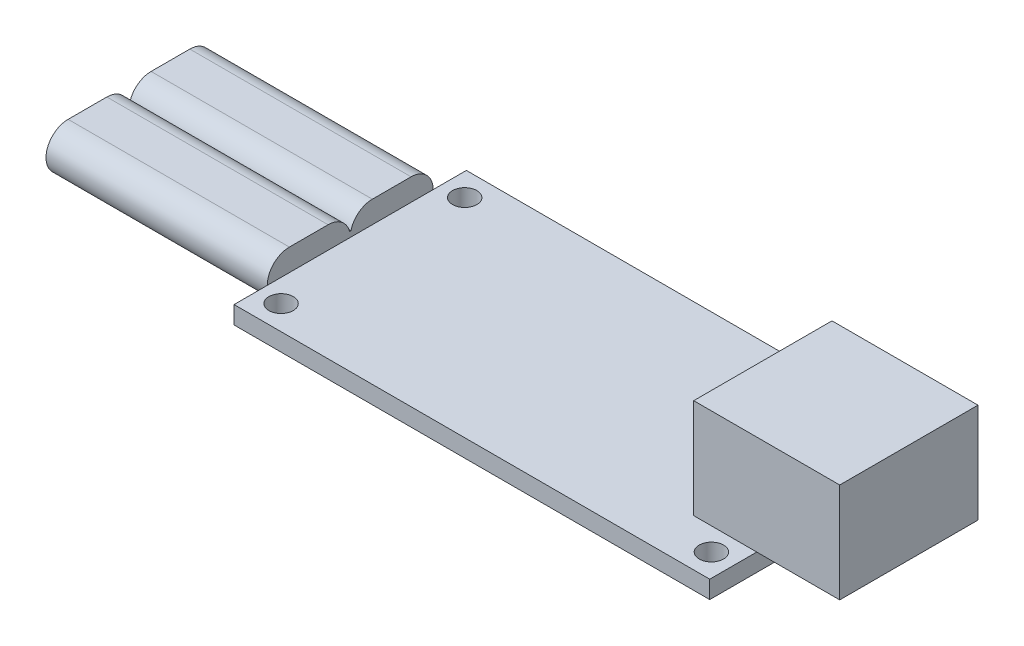
SolidWorks part; units mm, degrees
ref_plane "Płaszczyzna przednia" through (0, 0, 0) normal (0, 0, 1) x (1, 0, 0)
ref_plane "Płaszczyzna górna" through (0, 0, 0) normal (0, 1, 0) x (1, 0, 0)
ref_plane "Płaszczyzna prawa" through (0, 0, 0) normal (1, 0, 0) x (0, 0, -1)
sketch "Sketch1" plane through (0, 0, 0) normal (0, 1, 0) x (1, 0, 0)
  line L0 (21.5, 21) -> (21.5, 10.5) construction
  line L1 (0, 0) -> (43, 0)
  line L2 (0, 0) -> (0, 21)
  line L3 (0, 21) -> (43, 21)
  line L4 (43, 0) -> (43, 21)
  line L5 (21.5, 10.5) -> (0, 10.5) construction
  line L6 (2.05, 18.8) -> (40.95, 2.2) construction
  line L7 (40.95, 18.8) -> (2.05, 2.2) construction
  circle A0 centre (2.05, 18.8) radius 1.1
  circle A1 centre (40.95, 18.8) radius 1.1
  circle A2 centre (40.95, 2.2) radius 1.1
  circle A3 centre (2.05, 2.2) radius 1.1
  point P16 (21.5, 10.5)
  dimension "D3" = 2.2
  dimension "D6" = 38.9
  dimension "D7" = 16.6
  dimension "D1" = 21
  dimension "D2" = 43
  dimension "D4" = 2
  dimension "D5" = 2
extrude "Boss-Extrude1" add sketch "Sketch1" along normal blind 1.6
sketch "Sketch2" plane through (0, 0, 0) normal (-1, 0, 0) x (0, 0, 1)
  line L0 (-21, 1.6) -> (0, 1.6) construction
  line L1 (-12.5, 1.6) -> (-16, 1.6) construction
  line L2 (-12.5, -0.4) -> (-16, -0.4)
  line L3 (-12.5, 3.6) -> (-16, 3.6)
  line L4 (-8.5, 1.6) -> (-5, 1.6) construction
  line L5 (-8.5, 3.6) -> (-5, 3.6)
  line L6 (-8.5, -0.4) -> (-5, -0.4)
  line L7 (-14.25, 1.6) -> (-6.75, 1.6) construction
  line L8 (-10.5, 0) -> (-10.5, 1.6) construction
  line L9 (-21, 0) -> (0, 0) construction
  circle A0 centre (-14.25, 1.6) radius 2.0409 construction
  circle A1 centre (-6.75, 1.6) radius 1.5789 construction
  arc A2 (-12.5, -0.4) -> (-12.5, 3.6) centre (-12.5, 1.6) ccw
  arc A3 (-16, 3.6) -> (-16, -0.4) centre (-16, 1.6) ccw
  arc A4 (-8.5, 3.6) -> (-8.5, -0.4) centre (-8.5, 1.6) ccw
  arc A5 (-5, -0.4) -> (-5, 3.6) centre (-5, 1.6) ccw
  circle A6 centre (-10.5, 1.6) radius 0.5
  point P8 (-14.25, 1.6)
  point P15 (-6.75, 1.6)
  point P20 (-10.5, 1.6)
  point P21 (-18, 1.6)
  point P22 (-3, 1.6)
  line M13 (-21, 0) -> (0, 0)
  line M15 (0, 1.6) -> (-21, 1.6)
  dimension "D1" = 15
  dimension "D4" = 1
  dimension "D2" = 7.5
  dimension "D3" = 4
extrude "Boss-Extrude2" add sketch "Sketch2" along normal blind 20 contours A6 A2 L3 A3 M15 | A6 A3 A2 M15 M13 | A3 L2 A2 M13 | A2 A6 M15 | A4 A6 A2 | A6 A4 M15 | A4 A6 M15 | A6 A2 M15 | A2 A6 A4 | A6 A4 A5 M13 M15 | A6 A5 L5 A4 M15 | L6 A5 A4 M13 region at (0, -0.1877, -14.25) region at (0, 0.8191, -14.3094) region at (0, 1.3969, -10.7231) region at (0, 1.2256, -10.5) region at (0, -0.1877, -6.75) region at (0, 0.8191, -6.6906) region at (0, 2.5388, -14.3001) region at (0, 1.8031, -10.7231) region at (0, 1.9744, -10.5) region at (0, 1.3969, -10.2769) region at (0, 1.8031, -10.2769) region at (0, 2.5388, -6.6999)
sketch "Sketch3" plane through (0, 1.6, 0) normal (0, 1, 0) x (1, 0, 0)
  line L0 (0, 10.5) -> (37.3, 10.5) construction
  line L1 (37.3, 16.75) -> (50.5, 16.75)
  line L2 (37.3, 16.75) -> (37.3, 4.25)
  line L3 (37.3, 4.25) -> (50.5, 4.25)
  line L4 (50.5, 16.75) -> (50.5, 4.25)
  line L5 (0, 18) -> (0, 3) construction
  dimension "D1" = 12.5
  dimension "D2" = 13.2
  dimension "D3" = 50.5
extrude "Boss-Extrude3" add sketch "Sketch3" along normal blind 9
